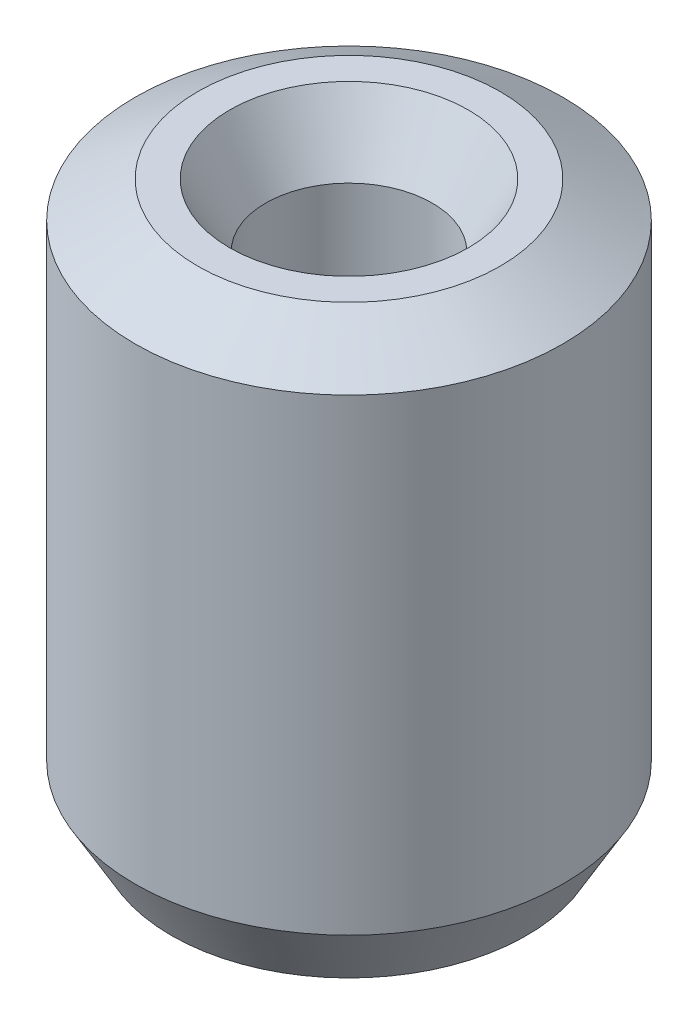
SolidWorks part; units mm, degrees
ref_plane "Front Plane" through (0, 0, 0) normal (0, 0, 1) x (1, 0, 0)
ref_plane "Top Plane" through (0, 0, 0) normal (0, 1, 0) x (1, 0, 0)
ref_plane "Right Plane" through (0, 0, 0) normal (1, 0, 0) x (0, 0, -1)
sketch "Sketch1" plane through (0, 0, 0) normal (0, 1, 0) x (1, 0, 0)
  circle A0 centre (0, 0) radius 7.5
  dimension "SLEEVE_OD" = 15
extrude "Boss-Extrude1" add sketch "Sketch1" along normal blind 19.8699
sketch "Sketch2" plane through (0, 0, 0) normal (0, 1, 0) x (1, 0, 0)
  circle A0 centre (0, 0) radius 2.9216
  dimension "BORE_D" = 5.8432
extrude "Cut-Extrude1" cut sketch "Sketch2" along normal through all
chamfer "Chamfer1" distance 1.267 angle 60 4 edges at (0, 19.8699, 2.9216) (0, 0, 2.9216) (0, 0, 7.5) (0, 19.8699, 7.5) first distance on face at (0, 19.8699, 2.9216) first distance on face at (0, 0, 2.9216) first distance on face at (0, 19.8699, 7.5)
